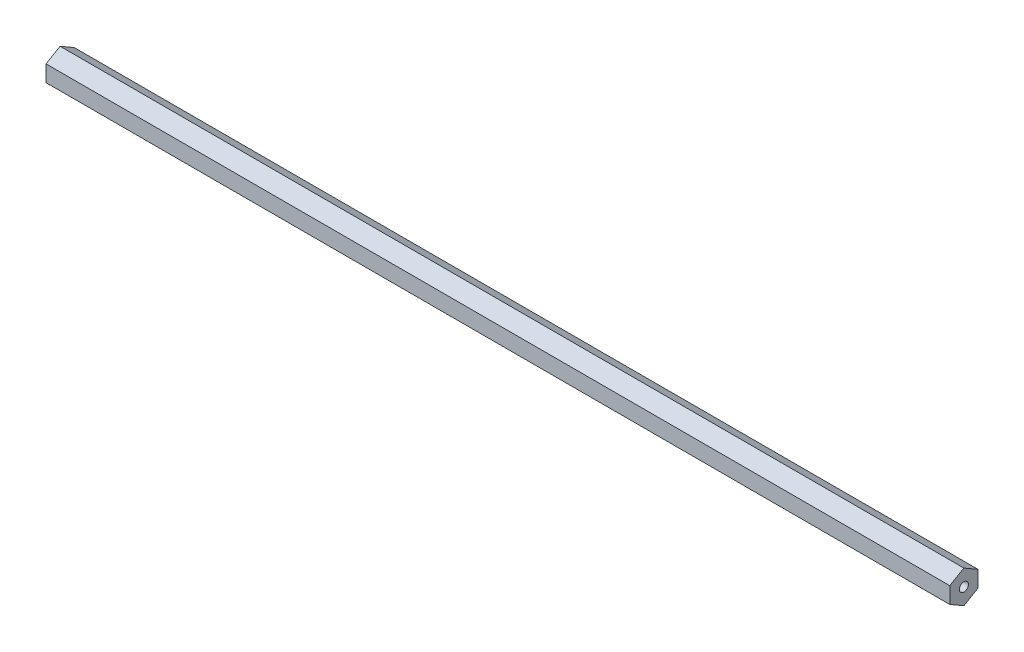
SolidWorks part; units mm, degrees
material "7075-T6 (SN)"
ref_plane "Front Plane" through (0, 0, 0) normal (0, 0, 1) x (1, 0, 0)
ref_plane "Top Plane" through (0, 0, 0) normal (0, 1, 0) x (1, 0, 0)
ref_plane "Right Plane" through (0, 0, 0) normal (1, 0, 0) x (0, 0, -1)
sketch "Sketch1" plane through (0, 0, 0) normal (1, 0, 0) x (0, 0, -1)
  line L1 (0, 7.3323) -> (-6.35, 3.6662)
  line L2 (-6.35, 3.6662) -> (-6.35, -3.6662)
  line L3 (-6.35, -3.6662) -> (0, -7.3323)
  line L4 (0, -7.3323) -> (6.35, -3.6662)
  line L5 (6.35, -3.6662) -> (6.35, 3.6662)
  line L6 (6.35, 3.6662) -> (0, 7.3323)
  circle A2 centre (0, 0) radius 6.35 construction
  dimension "D2" = 12.7
extrude "Boss-Extrude1" add sketch "Sketch1" along normal mid plane 406.4 contours L5 L6 L1 L2 L3 L4 region at (0, 0, 0)
sketch "Sketch3" plane through (-200.8187, 0, 0) normal (-1, 0, 0) x (0, 0, 1)
  circle A0 centre (0, 0) radius 6.35
  dimension "D1" = 12.7
hole_wizard "#10-32 Tapped Hole1" positions "3DSketch1" profile "Sketch4" tap size "#10-32" standard "ANSI Inch"
sketch3d "3DSketch1"
  point P9 (203.2, 0, 0)
  point P27 (-203.2, 0, 0)
sketch "Sketch4" plane through (203.2, 0, 0) normal (0, 1, 0) x (0, 0, -1)
  line L0 (0, 0) -> (0, 17.5608)
  line L1 (0, 17.5608) -> (2.0193, 16.3474)
  line L2 (2.0193, 16.3474) -> (2.0193, 0)
  line L5 (2.0193, 0) -> (0, 0)
  line L10 (0, 17.5608) -> (-2.0193, 16.3474) construction
  line L11 (0, -6.35) -> (0, 107.95) construction
  dimension "Tap Drill Dia." = 4.0386
  dimension "Tap Drill Depth" = 16.3474
  dimension "Drill Angle" = 118
cosmetic thread "Hole Thread2"
cosmetic thread "Hole Thread3"
